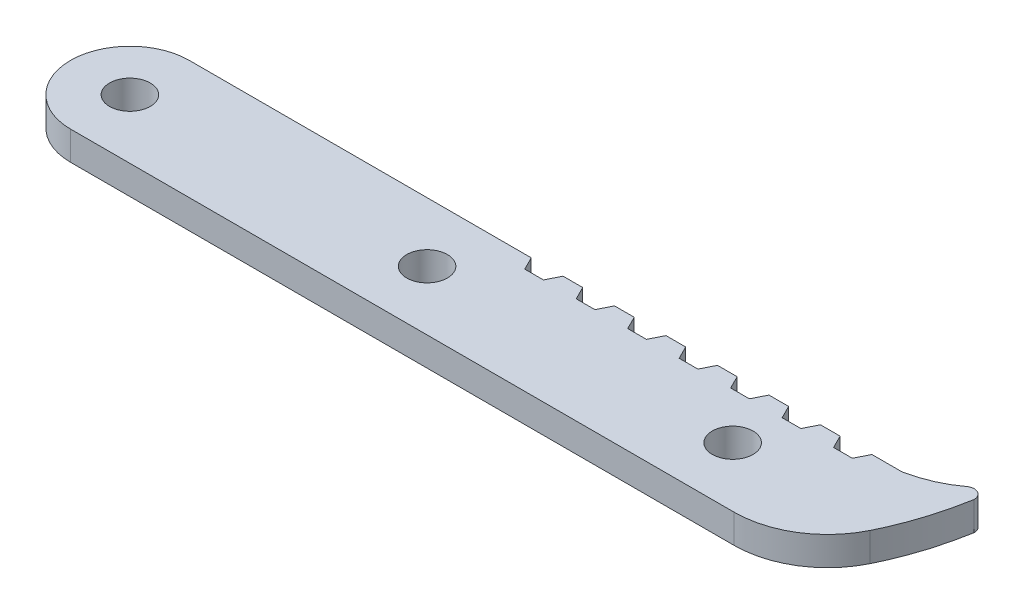
SolidWorks part; units mm, degrees
material "PET"
ref_plane "Front" through (0, 0, 0) normal (0, 0, 1) x (1, 0, 0)
ref_plane "Top" through (0, 0, 0) normal (0, 1, 0) x (1, 0, 0)
ref_plane "Right" through (0, 0, 0) normal (1, 0, 0) x (0, 0, -1)
sketch "Sketch1" plane through (0, 0, 0) normal (0, 1, 0) x (1, 0, 0)
  line L1 (-62.8447, 8.7002) -> (13.3553, 8.7002)
  line L3 (-62.8447, -3.9998) -> (13.3553, -3.9998)
  line L5 (-62.8447, 8.7002) -> (13.3553, -3.9998) construction
  line L6 (-62.8447, -3.9998) -> (13.3553, 8.7002) construction
  arc A0 (-62.8447, 8.7002) -> (-62.8447, -3.9998) centre (-62.8447, 2.3502) ccw
  arc A2 (13.3553, 8.7002) -> (13.3553, -3.9998) centre (13.3553, 2.3502) cw
  point P4 (-24.7447, 2.3502)
  dimension "D1" = 76.2
  dimension "D2" = 12.7
extrude "Boss-Extrude1" add sketch "Sketch1" along normal blind 3.075
sketch "Sketch2" plane through (0, 3.075, 0) normal (0, 1, 0) x (1, 0, 0)
  circle A0 centre (-62.8447, 2.3502) radius 2.175
  circle A1 centre (-31.0947, 2.3502) radius 2.175
  circle A2 centre (1.5553, 2.3502) radius 2.175
  arc A3 (13.3553, -3.9998) -> (13.3553, 8.7002) centre (13.3553, 2.3502) ccw construction
  dimension "D1" = 31.75
  dimension "D2" = 4.35
  dimension "D3" = 4.35
  dimension "D4" = 4.35
  dimension "D5" = 11.8
extrude "Cut-Extrude2" cut sketch "Sketch2" against normal blind 6.35 contours A1 | A0 | A2
sketch "Sketch3" plane through (0, 3.075, 0) normal (0, 1, 0) x (1, 0, 0)
  line L2 (13.3553, 8.7002) -> (13.3553, 2.3502)
  line L7 (19.7053, 2.3502) -> (19.7053, 9.9994)
  line L8 (19.7053, 2.3502) -> (13.3553, 2.3502)
  arc A0 (13.3553, -3.9998) -> (13.3553, 8.7002) centre (13.3553, 2.3502) ccw construction
  arc A1 (19.7053, 9.9994) -> (18.1023, 10.7971) centre (18.7053, 9.9994) ccw
  spline S0 degree 3 poles (13.3553, 8.7002) (15.2148, 9.1115) (16.7971, 9.8105) (18.1023, 10.7971) knots 0 0 0 0 0.482998 0.482998 0.482998 0.482998
  point P4 (25.0274, 5.3951)
  dimension "D1" = 1
  dimension "D2" = 7.6492
extrude "Boss-Extrude2" add sketch "Sketch3" against normal up to vertex (3.075 mm away) up to point (13.3553, 0, -8.7002)
sketch "Sketch4" plane through (0, 3.075, 0) normal (0, 1, 0) x (1, 0, 0)
  line L1 (19.7053, 9.9994) -> (21.2841, -6.7751)
  line L2 (21.2841, -6.7751) -> (10.6472, -6.7751)
  spline S0 degree 2 poles (19.7053, 9.9994) (17.9224, -0.2645) (10.6472, -6.7751) knots 0 0 0 1 1 1
extrude "Cut-Extrude3" cut sketch "Sketch4" against normal blind 10
fillet "Fillet1" radius 10 1 edges at (13.3553, 1.5375, 3.9998)
sketch "Sketch5" plane through (0, 3.075, 0) normal (0, 1, 0) x (1, 0, 0)
  line L0 (-4.3147, 8.7002) -> (-0.9147, 8.7002)
  line L1 (13.3553, 8.7002) -> (-62.8447, 8.7002) construction
  line L3 (-9.8147, 8.7002) -> (-9.1147, 7.306)
  line L4 (-9.1147, 7.306) -> (-7.1147, 7.306)
  line L5 (-7.1147, 7.306) -> (-6.4147, 8.7002)
  line L14 (-4.3147, 8.7002) -> (-3.6147, 7.306)
  line L18 (-9.8147, 8.7002) -> (-6.4147, 8.7002)
  line L19 (-3.6147, 7.306) -> (-1.6147, 7.306)
  line L20 (-1.6147, 7.306) -> (-0.9147, 8.7002)
  line L21 (1.1853, 8.7002) -> (4.5853, 8.7002)
  line L22 (1.1853, 8.7002) -> (1.8853, 7.306)
  line L23 (1.8853, 7.306) -> (3.8853, 7.306)
  line L24 (3.8853, 7.306) -> (4.5853, 8.7002)
  line L25 (6.6853, 8.7002) -> (10.0853, 8.7002)
  line L26 (6.6853, 8.7002) -> (7.3853, 7.306)
  line L27 (7.3853, 7.306) -> (9.3853, 7.306)
  line L28 (9.3853, 7.306) -> (10.0853, 8.7002)
  line L29 (-15.3147, 8.7002) -> (-11.9147, 8.7002)
  line L30 (-15.3147, 8.7002) -> (-14.6147, 7.306)
  line L31 (-14.6147, 7.306) -> (-12.6147, 7.306)
  line L32 (-12.6147, 7.306) -> (-11.9147, 8.7002)
  line L33 (-20.8147, 8.7002) -> (-17.4147, 8.7002)
  line L34 (-20.8147, 8.7002) -> (-20.1147, 7.306)
  line L35 (-20.1147, 7.306) -> (-18.1147, 7.306)
  line L36 (-18.1147, 7.306) -> (-17.4147, 8.7002)
  line L37 (-26.3147, 8.7002) -> (-22.9147, 8.7002)
  line L38 (-26.3147, 8.7002) -> (-25.6147, 7.306)
  line L39 (-25.6147, 7.306) -> (-23.6147, 7.306)
  line L40 (-23.6147, 7.306) -> (-22.9147, 8.7002)
  dimension "D1" = 4
  dimension "D2" = 4
  dimension "D3" = 2
  dimension "D4" = 1.56
  dimension "D5" = 1.56
extrude "Cut-Extrude4" cut sketch "Sketch5" against normal blind 10
